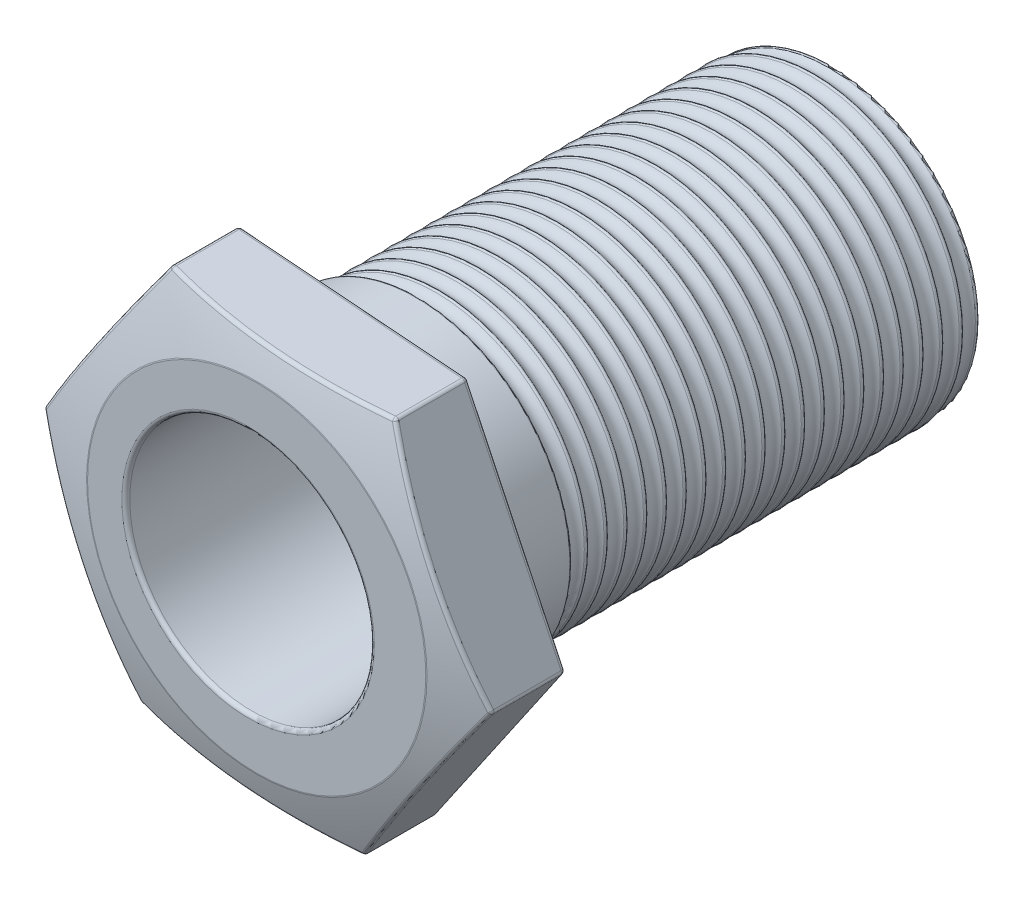
SolidWorks part; units mm, degrees
ref_plane "Front Plane" through (0, 0, 0) normal (0, 0, 1) x (1, 0, 0)
ref_plane "Top Plane" through (0, 0, 0) normal (0, 1, 0) x (1, 0, 0)
ref_plane "Right Plane" through (0, 0, 0) normal (1, 0, 0) x (0, 0, -1)
sketch "Sketch1" plane through (0, 0, 0) normal (0, 0, 1) x (1, 0, 0)
  line L1 (12.7404, -39.5734) -> (9.474, -44.3341)
  line L2 (9.474, -44.3341) -> (11.9636, -49.5432)
  line L3 (11.9636, -49.5432) -> (17.7197, -49.9917)
  line L4 (17.7197, -49.9917) -> (20.9861, -45.231)
  line L5 (20.9861, -45.231) -> (18.4964, -40.0219)
  line L6 (18.4964, -40.0219) -> (12.7404, -39.5734)
  circle A0 centre (15.23, -44.7825) radius 5 construction
  dimension "D1" = 10
extrude "Boss-Extrude1" add sketch "Sketch1" along normal blind 2.3
sketch "Sketch2" plane through (0, 0, 2.3) normal (0, 0, 1) x (1, 0, 0)
  circle A0 centre (15.23, -44.7825) radius 3.9
extrude "Boss-Extrude2" add sketch "Sketch2" against normal blind 14.8
sketch "Sketch3" plane through (0, 0, 2.3) normal (0, 0, 1) x (1, 0, 0)
  circle A0 centre (15.23, -44.7825) radius 3.1
extrude "Cut-Extrude1" cut sketch "Sketch3" against normal blind 14.8
ref_plane "Plane1" through (-3.376, -43.333, 0) normal (0.0777, 0.997, 0) x (0.997, -0.0777, 0)
sketch "Sketch4" plane through (-3.376, -43.333, 0) normal (0.0777, 0.997, 0) x (0.997, -0.0777, 0)
  line L0 (22.5624, 12.5) -> (14.7624, 12.5) construction
  line L1 (22.5624, 2) -> (23.6537, 2)
  line L2 (23.6537, 2) -> (23.6396, 12.5)
  line L3 (23.6396, 12.5) -> (22.5624, 12.5)
  line L4 (18.6624, 12.5) -> (18.6624, 8.25) construction
  arc A0 (22.5624, 12.5) -> (22.5624, 12) centre (22.5624, 12.25) ccw
  arc A1 (22.5624, 12) -> (22.5624, 11.5) centre (22.5624, 11.75) ccw
  arc A2 (22.5624, 11.5) -> (22.5624, 11) centre (22.5624, 11.25) ccw
  arc A3 (22.5624, 11) -> (22.5624, 10.5) centre (22.5624, 10.75) ccw
  arc A4 (22.5624, 10.5) -> (22.5624, 10) centre (22.5624, 10.25) ccw
  arc A5 (22.5624, 10) -> (22.5624, 9.5) centre (22.5624, 9.75) ccw
  arc A6 (22.5624, 9.5) -> (22.5624, 9) centre (22.5624, 9.25) ccw
  arc A7 (22.5624, 9) -> (22.5624, 8.5) centre (22.5624, 8.75) ccw
  arc A8 (22.5624, 8.5) -> (22.5624, 8) centre (22.5624, 8.25) ccw
  arc A9 (22.5624, 8) -> (22.5624, 7.5) centre (22.5624, 7.75) ccw
  arc A10 (22.5624, 7.5) -> (22.5624, 7) centre (22.5624, 7.25) ccw
  arc A11 (22.5624, 7) -> (22.5624, 6.5) centre (22.5624, 6.75) ccw
  arc A12 (22.5624, 6.5) -> (22.5624, 6) centre (22.5624, 6.25) ccw
  arc A13 (22.5624, 6) -> (22.5624, 5.5) centre (22.5624, 5.75) ccw
  arc A14 (22.5624, 5.5) -> (22.5624, 5) centre (22.5624, 5.25) ccw
  arc A15 (22.5624, 5) -> (22.5624, 4.5) centre (22.5624, 4.75) ccw
  arc A16 (22.5624, 4.5) -> (22.5624, 4) centre (22.5624, 4.25) ccw
  arc A17 (22.5624, 4) -> (22.5624, 3.5) centre (22.5624, 3.75) ccw
  arc A18 (22.5624, 3.5) -> (22.5624, 3) centre (22.5624, 3.25) ccw
  arc A19 (22.5624, 3) -> (22.5624, 2.5) centre (22.5624, 2.75) ccw
  arc A20 (22.5624, 2.5) -> (22.5624, 2) centre (22.5624, 2.25) ccw
  dimension "D1" = 0.5
  dimension "D2" = 21
revolve "Cut-Revolve1" cut sketch "Sketch4" angle 360 about L4
fillet "Fillet1" radius 0.05 23 edges at (11.33, -44.7825, -2) (11.33, -44.7825, -12.5) (11.33, -44.7825, -2.5) (11.33, -44.7825, -3) (11.33, -44.7825, -3.5) (11.33, -44.7825, -4) (11.33, -44.7825, -4.5) (11.33, -44.7825, -5) (11.33, -44.7825, -5.5) (11.33, -44.7825, -6) (11.33, -44.7825, -6.5) (11.33, -44.7825, -7) (11.33, -44.7825, -7.5) (11.33, -44.7825, -8) (11.33, -44.7825, -8.5) (11.33, -44.7825, -9) (11.33, -44.7825, -9.5) (11.33, -44.7825, -10) (11.33, -44.7825, -10.5) (11.33, -44.7825, -11) (11.33, -44.7825, -11.5) (11.33, -44.7825, -12) (18.33, -44.7825, -12.5)
sketch "Sketch5" plane through (-3.376, -43.333, 0) normal (0.0777, 0.997, 0) x (0.997, -0.0777, 0)
  line L0 (12.8889, -2.3) -> (12.8889, 0) construction
  line L1 (21.5491, -2.3) -> (15.7756, -2.3) construction
  line L2 (12.8889, -1.7) -> (12.297, -1.7)
  line L3 (12.297, -1.7) -> (12.6756, -3.9175)
  line L4 (12.6756, -3.9175) -> (14.5796, -2.3)
  line L5 (18.8796, -2.3) -> (18.8796, -0.7114) construction
  line L6 (15.7756, 0) -> (12.8889, 0) construction
  arc A0 (12.8889, -1.7) -> (14.5796, -2.3) centre (18.8796, 12.4993) ccw
  dimension "D1" = 4.3
  dimension "D2" = 1.7
revolve "Cut-Revolve2" cut sketch "Sketch5" angle 360 about L5
fillet "Fillet2" radius 0.1 20 edges at (18.4964, -40.0219, 0.9159) (20.9861, -45.231, 0.9378) (17.7197, -49.9917, 0.9159) (11.9636, -49.5432, 0.8721) (9.474, -44.3341, 0.85) (12.7404, -39.5734, 0.8721) (11.1072, -41.9538, 0) (10.7188, -46.9387, 0) (14.8417, -49.7674, 0) (19.3529, -47.6113, 0) (19.7413, -42.6264, 0) (15.6184, -39.7976, 0) (19.13, -44.7825, 0) (19.7403, -42.6245, 2.1412) (19.3517, -47.6131, 2.1412) (14.8373, -49.7671, 2.0767) (10.7179, -46.9367, 2.0121) (11.1059, -41.9556, 2.0121) (15.614, -39.7973, 2.0767) (19.7466, -44.7994, 2.3)
fillet "Fillet3" radius 0.1 1 edges at (18.33, -44.7825, 2.3)
